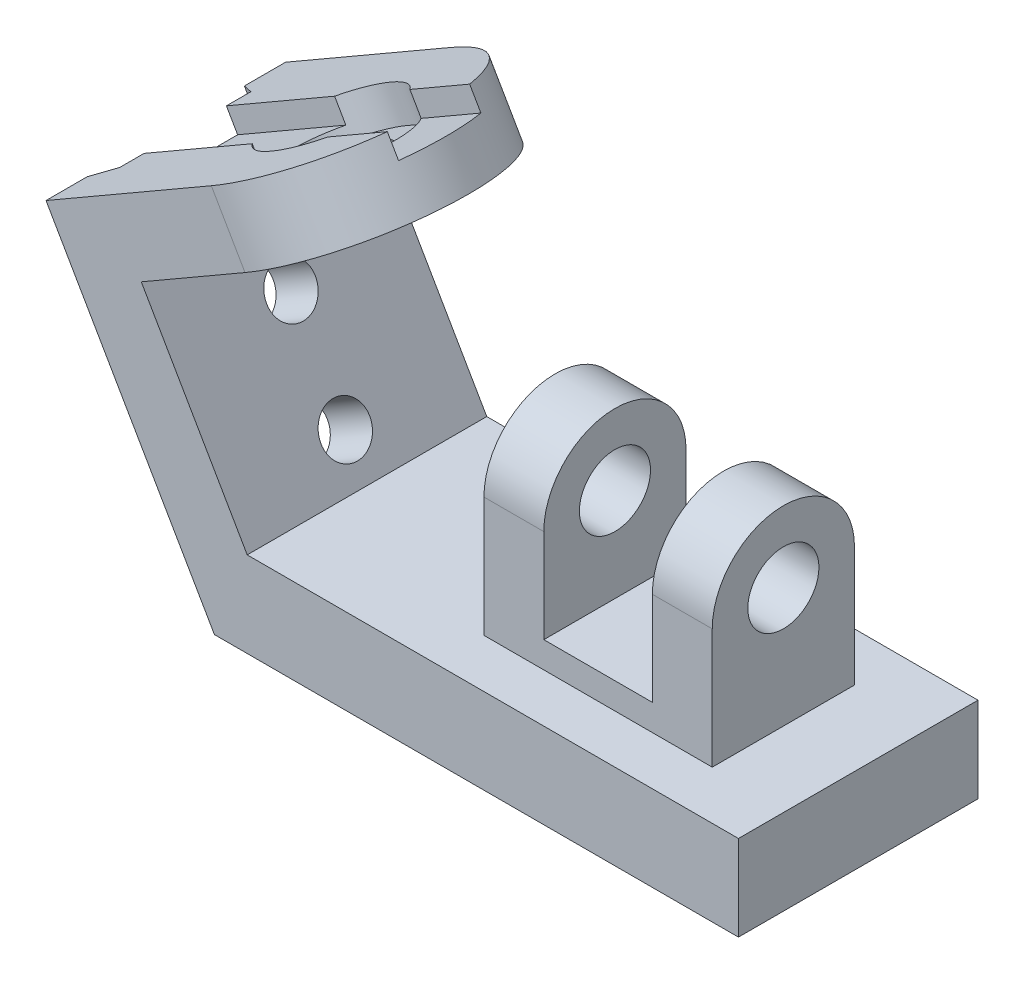
SolidWorks part; units mm, degrees
ref_plane "前基準面" through (0, 0, 0) normal (0, 0, 1) x (1, 0, 0)
ref_plane "上基準面" through (0, 0, 0) normal (0, 1, 0) x (1, 0, 0)
ref_plane "右基準面" through (0, 0, 0) normal (1, 0, 0) x (0, 0, -1)
sketch "草圖1" plane through (0, 0, 0) normal (0, 0, 1) x (1, 0, 0)
  line L0 (0, 0) -> (82.6307, 0) construction
  line L1 (0, 0) -> (0, 78.092) construction
  line L2 (0, 0) -> (-45, 77.9423)
  line L3 (0, 0) -> (140, 0)
  line L4 (140, 0) -> (140, 22.8306)
  line L5 (140, 22.8306) -> (8.758, 22.8306)
  line L6 (8.758, 22.8306) -> (-28.5455, 87.4423)
  line L7 (-28.5455, 87.4423) -> (-45, 77.9423)
  dimension "D1" = 60
  dimension "D2" = 90
  dimension "D3" = 140
  dimension "D4" = 22.8306
  dimension "D5" = 19
extrude "填料-伸長1" add sketch "草圖1" along normal mid plane 64
sketch "草圖2" plane through (-45, 77.9423, 0) normal (-0.5, 0.866, 0) x (0.866, 0.5, 0)
  line L0 (0, -32) -> (51, -32)
  line L1 (0, 32) -> (51, 32)
  line L2 (19, -32) -> (0, -32) construction
  line L3 (19, 32) -> (0, 32) construction
  line L4 (0, -32) -> (0, 32) construction
  line L9 (19, 32) -> (0, 32)
  line L10 (0, 32) -> (0, -32)
  line L11 (0, -32) -> (19, -32)
  line L12 (19, -32) -> (19, 32)
  line L13 (19, 32) -> (0, 32)
  line L15 (0, -32) -> (19, -32)
  line L16 (19, -32) -> (19, 32)
  arc A0 (51, 32) -> (51, -32) centre (51, 0) cw
  line M6 (19, -32) -> (19, 32)
  dimension "D1" = 51
  dimension "D2" = 0
extrude "填料-伸長2" add sketch "草圖2" against normal blind 18 contours A0 L1 L0 M6 region at (-3.4197, 101.9487, 0)
sketch "草圖4" plane through (-45, 77.9423, 0) normal (-0.5, 0.866, 0) x (0.866, 0.5, 0)
  line L0 (0, 0) -> (36.9962, 0) construction
  line L1 (0, -32) -> (0, 32) construction
  line L2 (0, 21) -> (6, 17.5359)
  line L3 (6, 17.5359) -> (6, -17.5359)
  line L4 (6, -17.5359) -> (0, -21)
  line L5 (0, -21) -> (0, 21)
  line L6 (51, 32) -> (0, 32) construction
  dimension "D1" = 42
  dimension "D2" = 30
  dimension "D3" = 6
extrude "除料-伸長1" cut sketch "草圖4" against normal through all
sketch "草圖5" plane through (-45, 77.9423, 0) normal (-0.5, 0.866, 0) x (0.866, 0.5, 0)
  line L0 (6, 0) -> (90.6775, 0) construction
  line L1 (6, -17.5359) -> (6, 17.5359) construction
  line L2 (51, 32) -> (0, 32) construction
  line L3 (51, -32) -> (0, -32) construction
  line L5 (97.2909, 11) -> (-13.4726, 11)
  line L6 (97.2909, 11) -> (97.2909, -11)
  line L7 (97.2909, -11) -> (-13.4726, -11)
  line L8 (-13.4726, 11) -> (-13.4726, -11)
  dimension "D1" = 22
extrude "除料-伸長2" cut sketch "草圖5" against normal blind 6
sketch "草圖6" plane through (-45, 77.9423, 0) normal (-0.5, 0.866, 0) x (0.866, 0.5, 0)
  line L0 (0, 0) -> (95.2132, 0) construction
  line L1 (51, 32) -> (0, 32) construction
  line L2 (51, -32) -> (0, -32) construction
  line L3 (0, 21) -> (0, 32) construction
  circle A0 centre (51, 0) radius 16
  circle A2 centre (51, 0) radius 9.5
  line M3 (6, 11) -> (81.05, 11)
  dimension "D1" = 32
  dimension "D3" = 19
  dimension "D2" = 51
extrude "除料-伸長3" cut sketch "草圖6" against normal blind 36 contours L0 A2 | A2 L0 region at (-0.8327, 103.4423, 4.0319) region at (-0.8327, 103.4423, -4.0319)
extrude "除料-伸長4" cut sketch "草圖6<3>" against normal blind 9 contours L0 A2 | A2 L0 | A0 L0 A2 M3 | A0 M3 | L0 A0 A2 region at (-0.8327, 103.4423, -9.8384) region at (-0.8327, 103.4423, 4.0319) region at (-0.8327, 103.4423, -4.0319) region at (10.2091, 109.8173, 0.3578) region at (-0.8327, 103.4423, -13.0295)
sketch "草圖6<3>" plane through (-45, 77.9423, 0) normal (-0.5, 0.866, 0) x (0.866, 0.5, 0) same geometry as "草圖6"
sketch "草圖7" plane through (5.1962, 3, 0) normal (-0.866, -0.5, 0) x (0, 0, 1)
  line L0 (0, -3.4641) -> (0, 94.1816) construction
  line L2 (21, 90) -> (21, 0) construction
  line L3 (-21, 0) -> (-21, 90) construction
  line L4 (11, 84) -> (-11, 84) construction
  circle A0 centre (0, 56) radius 6.5
  circle A1 centre (0, 27) radius 6.5
  dimension "D1" = 13
  dimension "D2" = 28
  dimension "D3" = 29
extrude "除料-伸長5" cut sketch "草圖7" against normal through all
ref_plane "平面1" through (89.5, 0, 0) normal (1, 0, 0) x (0, 0, -1)
sketch "草圖8" plane through (89.5, 0, 0) normal (1, 0, 0) x (0, 0, -1)
  line L0 (-32, 22.8306) -> (32, 22.8306) construction
  line L1 (-32, 22.8306) -> (32, 22.8306) construction
  line L2 (0, 22.8306) -> (0, 73.7784) construction
  line L3 (-19, 29.8306) -> (19, 29.8306)
  line L5 (-32, 0) -> (-32, 22.8306) construction
  line L6 (32, 0) -> (32, 22.8306) construction
  line L7 (-19, 54.8306) -> (-19, 22.8306)
  line L8 (-19, 22.8306) -> (19, 22.8306)
  line L9 (19, 54.8306) -> (19, 22.8306)
  arc A0 (-19, 54.8306) -> (19, 54.8306) centre (0, 54.8306) cw
  circle A1 centre (0, 54.8306) radius 9.5
  dimension "D1" = 19
  dimension "D3" = 19
  dimension "D2" = 32
  dimension "D4" = 25
extrude "填料-伸長3" add sketch "草圖8" along normal mid plane 61 contours L9 L3 L7 L8 region at (89.5, 26.3306, 0)
extrude "填料-伸長4" add sketch "草圖8<3>" along normal blind 16 from offset 14.5 contours A0 L7 L3 L9 A1 region at (89.5, 42.3306, 18.4186)
sketch "草圖8<3>" plane through (89.5, 0, 0) normal (1, 0, 0) x (0, 0, -1) same geometry as "草圖8"
mirror "鏡射1" about plane through (89.5, 0, 0) normal (1, 0, 0) of "填料-伸長4"
